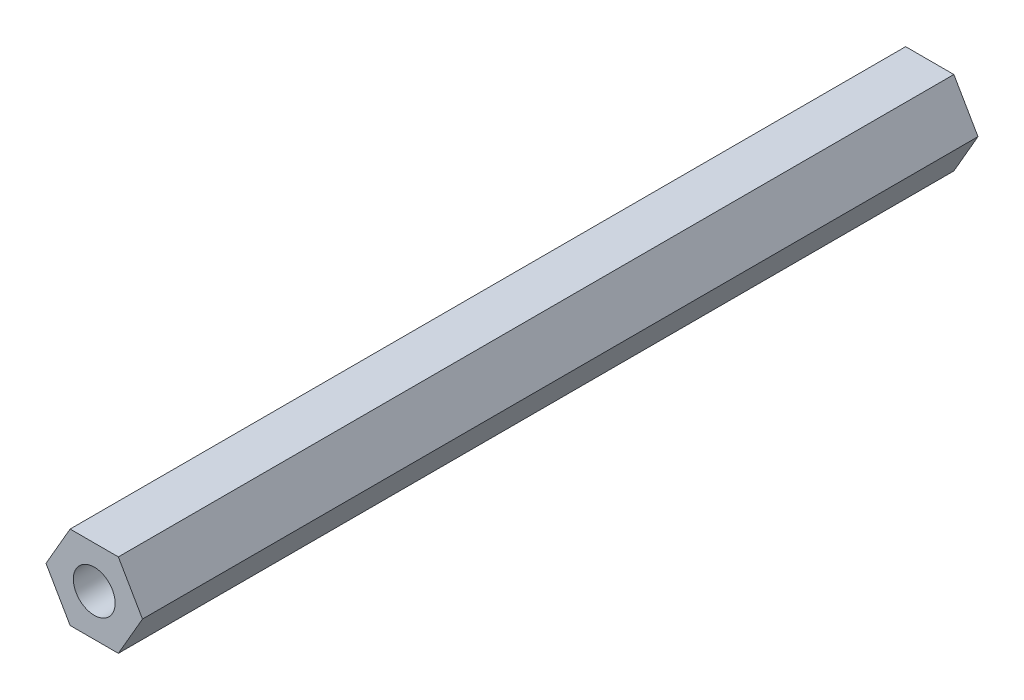
SolidWorks part; units mm, degrees
material "1060 Alloy"
ref_plane "Front Plane" through (0, 0, 0) normal (0, 0, 1) x (1, 0, 0)
ref_plane "Top Plane" through (0, 0, 0) normal (0, 1, 0) x (1, 0, 0)
ref_plane "Right Plane" through (0, 0, 0) normal (1, 0, 0) x (0, 0, -1)
sketch "Sketch1" plane through (0, 0, 0) normal (0, 0, 1) x (1, 0, 0)
  line L1 (3.6662, 6.35) -> (-3.6662, 6.35)
  line L2 (-3.6662, 6.35) -> (-7.3323, 0)
  line L3 (-7.3323, 0) -> (-3.6662, -6.35)
  line L4 (-3.6662, -6.35) -> (3.6662, -6.35)
  line L5 (3.6662, -6.35) -> (7.3323, 0)
  line L6 (7.3323, 0) -> (3.6662, 6.35)
  circle A0 centre (0, 0) radius 6.35 construction
  circle A1 centre (0, 0) radius 3.175
  dimension "D2" = 6.35
  dimension "D1" = 12.7
extrude "Boss-Extrude1" add sketch "Sketch1" along normal mid plane 127
